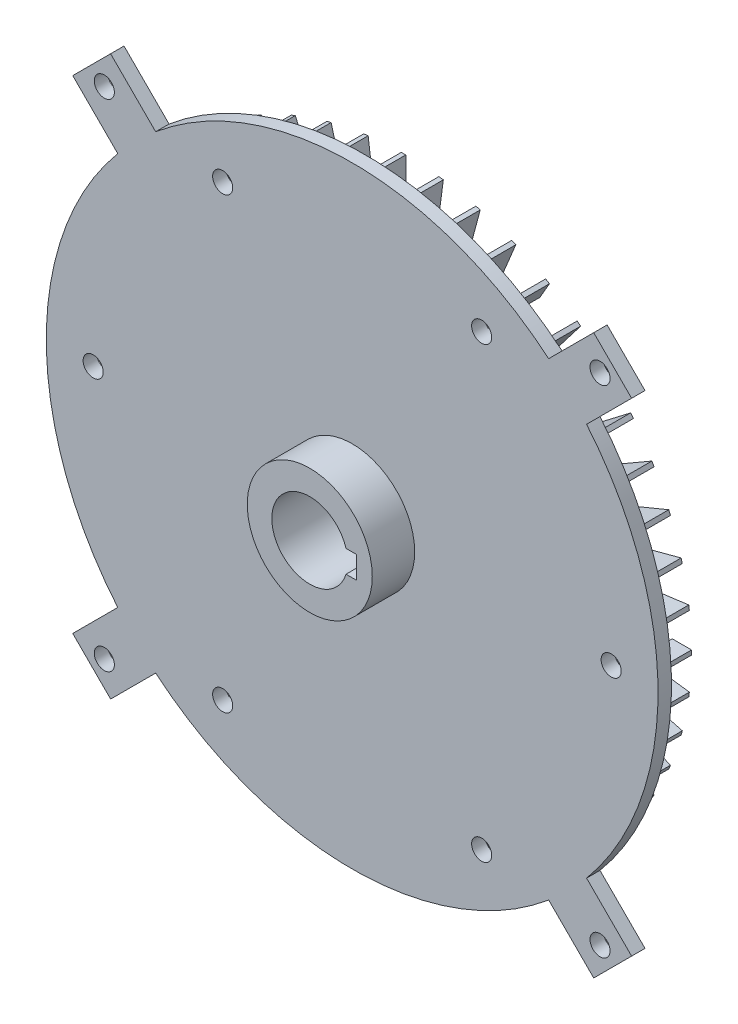
SolidWorks part; units mm, degrees
ref_plane "Спереди" through (0, 0, 0) normal (0, 0, 1) x (1, 0, 0)
ref_plane "Сверху" through (0, 0, 0) normal (0, 1, 0) x (1, 0, 0)
ref_plane "Справа" through (0, 0, 0) normal (1, 0, 0) x (0, 0, -1)
sketch "Эскиз1" plane through (0, 0, 0) normal (0, 0, 1) x (1, 0, 0)
  circle A0 centre (0, 0) radius 68.5
  circle A1 centre (0, 0) radius 8.5
extrude "Heat_spreader" add sketch "Эскиз1" along normal blind 3 from offset 30 offset against normal yes
sketch "Эскиз2" plane through (0, 0, 0) normal (0, 0, 1) x (1, 0, 0)
  line L0 (48.4368, 39.9515) -> (62.579, 54.0937)
  line L1 (62.579, 54.0937) -> (54.0937, 62.579)
  line L2 (54.0937, 62.579) -> (39.9515, 48.4368)
  line L3 (39.9515, 48.4368) -> (48.4368, 39.9515)
  line L4 (-39.9515, 48.4368) -> (-54.0937, 62.579)
  line L5 (-54.0937, 62.579) -> (-62.579, 54.0937)
  line L6 (-62.579, 54.0937) -> (-48.4368, 39.9515)
  line L7 (-48.4368, 39.9515) -> (-39.9515, 48.4368)
  line L8 (-48.4368, -39.9515) -> (-62.579, -54.0937)
  line L9 (-62.579, -54.0937) -> (-54.0937, -62.579)
  line L10 (-54.0937, -62.579) -> (-39.9515, -48.4368)
  line L11 (-39.9515, -48.4368) -> (-48.4368, -39.9515)
  line L12 (39.9515, -48.4368) -> (54.0937, -62.579)
  line L13 (54.0937, -62.579) -> (62.579, -54.0937)
  line L14 (62.579, -54.0937) -> (48.4368, -39.9515)
  line L15 (48.4368, -39.9515) -> (39.9515, -48.4368)
extrude "Tie_rod_ears" add sketch "Эскиз2" along normal blind 3 from offset 30 offset against normal yes
sketch "Эскиз3" plane through (0, 0, 0) normal (0, 0, 1) x (1, 0, 0)
  line L0 (26, -0.5) -> (64.5, -0.5)
  line L1 (64.5, -0.5) -> (64.5, 0.5)
  line L2 (64.5, 0.5) -> (26, 0.5)
  line L3 (26, 0.5) -> (26, -0.5)
  line L4 (25.8428, 2.898) -> (64.0135, 7.9232)
  line L5 (64.0135, 7.9232) -> (63.8829, 8.9147)
  line L6 (63.8829, 8.9147) -> (25.7123, 3.8894)
  line L7 (25.7123, 3.8894) -> (25.8428, 2.898)
  line L8 (25.2435, 6.2463) -> (62.4316, 16.2109)
  line L9 (62.4316, 16.2109) -> (62.1728, 17.1768)
  line L10 (62.1728, 17.1768) -> (24.9847, 7.2123)
  line L11 (24.9847, 7.2123) -> (25.2435, 6.2463)
  line L12 (24.2122, 9.4878) -> (59.7816, 24.2211)
  line L13 (59.7816, 24.2211) -> (59.3989, 25.145)
  line L14 (59.3989, 25.145) -> (23.8295, 10.4117)
  line L15 (23.8295, 10.4117) -> (24.2122, 9.4878)
  line L16 (22.7667, 12.567) -> (56.1086, 31.817)
  line L17 (56.1086, 31.817) -> (55.6086, 32.683)
  line L18 (55.6086, 32.683) -> (22.2667, 13.433)
  line L19 (22.2667, 13.433) -> (22.7667, 12.567)
  line L20 (20.9316, 15.4311) -> (51.4757, 38.8684)
  line L21 (51.4757, 38.8684) -> (50.8669, 39.6618)
  line L22 (50.8669, 39.6618) -> (20.3228, 16.2245)
  line L23 (20.3228, 16.2245) -> (20.9316, 15.4311)
  line L24 (18.7383, 18.0312) -> (45.9619, 45.2548)
  line L25 (45.9619, 45.2548) -> (45.2548, 45.9619)
  line L26 (45.2548, 45.9619) -> (18.0312, 18.7383)
  line L27 (18.0312, 18.7383) -> (18.7383, 18.0312)
  line L28 (16.2245, 20.3228) -> (39.6618, 50.8669)
  line L29 (39.6618, 50.8669) -> (38.8684, 51.4757)
  line L30 (38.8684, 51.4757) -> (15.4311, 20.9316)
  line L31 (15.4311, 20.9316) -> (16.2245, 20.3228)
  line L32 (13.433, 22.2667) -> (32.683, 55.6086)
  line L33 (32.683, 55.6086) -> (31.817, 56.1086)
  line L34 (31.817, 56.1086) -> (12.567, 22.7667)
  line L35 (12.567, 22.7667) -> (13.433, 22.2667)
  line L36 (10.4117, 23.8295) -> (25.145, 59.3989)
  line L37 (25.145, 59.3989) -> (24.2211, 59.7816)
  line L38 (24.2211, 59.7816) -> (9.4878, 24.2122)
  line L39 (9.4878, 24.2122) -> (10.4117, 23.8295)
  line L40 (7.2123, 24.9847) -> (17.1768, 62.1728)
  line L41 (17.1768, 62.1728) -> (16.2109, 62.4316)
  line L42 (16.2109, 62.4316) -> (6.2463, 25.2435)
  line L43 (6.2463, 25.2435) -> (7.2123, 24.9847)
  line L44 (3.8894, 25.7123) -> (8.9147, 63.8829)
  line L45 (8.9147, 63.8829) -> (7.9232, 64.0135)
  line L46 (7.9232, 64.0135) -> (2.898, 25.8428)
  line L47 (2.898, 25.8428) -> (3.8894, 25.7123)
  line L48 (0.5, 26) -> (0.5, 64.5)
  line L49 (0.5, 64.5) -> (-0.5, 64.5)
  line L50 (-0.5, 64.5) -> (-0.5, 26)
  line L51 (-0.5, 26) -> (0.5, 26)
  line L52 (-2.898, 25.8428) -> (-7.9232, 64.0135)
  line L53 (-7.9232, 64.0135) -> (-8.9147, 63.8829)
  line L54 (-8.9147, 63.8829) -> (-3.8894, 25.7123)
  line L55 (-3.8894, 25.7123) -> (-2.898, 25.8428)
  line L56 (-6.2463, 25.2435) -> (-16.2109, 62.4316)
  line L57 (-16.2109, 62.4316) -> (-17.1768, 62.1728)
  line L58 (-17.1768, 62.1728) -> (-7.2123, 24.9847)
  line L59 (-7.2123, 24.9847) -> (-6.2463, 25.2435)
  line L60 (-9.4878, 24.2122) -> (-24.2211, 59.7816)
  line L61 (-24.2211, 59.7816) -> (-25.145, 59.3989)
  line L62 (-25.145, 59.3989) -> (-10.4117, 23.8295)
  line L63 (-10.4117, 23.8295) -> (-9.4878, 24.2122)
  line L64 (-12.567, 22.7667) -> (-31.817, 56.1086)
  line L65 (-31.817, 56.1086) -> (-32.683, 55.6086)
  line L66 (-32.683, 55.6086) -> (-13.433, 22.2667)
  line L67 (-13.433, 22.2667) -> (-12.567, 22.7667)
  line L68 (-15.4311, 20.9316) -> (-38.8684, 51.4757)
  line L69 (-38.8684, 51.4757) -> (-39.6618, 50.8669)
  line L70 (-39.6618, 50.8669) -> (-16.2245, 20.3228)
  line L71 (-16.2245, 20.3228) -> (-15.4311, 20.9316)
  line L72 (-18.0312, 18.7383) -> (-45.2548, 45.9619)
  line L73 (-45.2548, 45.9619) -> (-45.9619, 45.2548)
  line L74 (-45.9619, 45.2548) -> (-18.7383, 18.0312)
  line L75 (-18.7383, 18.0312) -> (-18.0312, 18.7383)
  line L76 (-20.3228, 16.2245) -> (-50.8669, 39.6618)
  line L77 (-50.8669, 39.6618) -> (-51.4757, 38.8684)
  line L78 (-51.4757, 38.8684) -> (-20.9316, 15.4311)
  line L79 (-20.9316, 15.4311) -> (-20.3228, 16.2245)
  line L80 (-22.2667, 13.433) -> (-55.6086, 32.683)
  line L81 (-55.6086, 32.683) -> (-56.1086, 31.817)
  line L82 (-56.1086, 31.817) -> (-22.7667, 12.567)
  line L83 (-22.7667, 12.567) -> (-22.2667, 13.433)
  line L84 (-23.8295, 10.4117) -> (-59.3989, 25.145)
  line L85 (-59.3989, 25.145) -> (-59.7816, 24.2211)
  line L86 (-59.7816, 24.2211) -> (-24.2122, 9.4878)
  line L87 (-24.2122, 9.4878) -> (-23.8295, 10.4117)
  line L88 (-24.9847, 7.2123) -> (-62.1728, 17.1768)
  line L89 (-62.1728, 17.1768) -> (-62.4316, 16.2109)
  line L90 (-62.4316, 16.2109) -> (-25.2435, 6.2463)
  line L91 (-25.2435, 6.2463) -> (-24.9847, 7.2123)
  line L92 (-25.7123, 3.8894) -> (-63.8829, 8.9147)
  line L93 (-63.8829, 8.9147) -> (-64.0135, 7.9232)
  line L94 (-64.0135, 7.9232) -> (-25.8428, 2.898)
  line L95 (-25.8428, 2.898) -> (-25.7123, 3.8894)
  line L96 (-26, 0.5) -> (-64.5, 0.5)
  line L97 (-64.5, 0.5) -> (-64.5, -0.5)
  line L98 (-64.5, -0.5) -> (-26, -0.5)
  line L99 (-26, -0.5) -> (-26, 0.5)
  line L100 (-25.8428, -2.898) -> (-64.0135, -7.9232)
  line L101 (-64.0135, -7.9232) -> (-63.8829, -8.9147)
  line L102 (-63.8829, -8.9147) -> (-25.7123, -3.8894)
  line L103 (-25.7123, -3.8894) -> (-25.8428, -2.898)
  line L104 (-25.2435, -6.2463) -> (-62.4316, -16.2109)
  line L105 (-62.4316, -16.2109) -> (-62.1728, -17.1768)
  line L106 (-62.1728, -17.1768) -> (-24.9847, -7.2123)
  line L107 (-24.9847, -7.2123) -> (-25.2435, -6.2463)
  line L108 (-24.2122, -9.4878) -> (-59.7816, -24.2211)
  line L109 (-59.7816, -24.2211) -> (-59.3989, -25.145)
  line L110 (-59.3989, -25.145) -> (-23.8295, -10.4117)
  line L111 (-23.8295, -10.4117) -> (-24.2122, -9.4878)
  line L112 (-22.7667, -12.567) -> (-56.1086, -31.817)
  line L113 (-56.1086, -31.817) -> (-55.6086, -32.683)
  line L114 (-55.6086, -32.683) -> (-22.2667, -13.433)
  line L115 (-22.2667, -13.433) -> (-22.7667, -12.567)
  line L116 (-20.9316, -15.4311) -> (-51.4757, -38.8684)
  line L117 (-51.4757, -38.8684) -> (-50.8669, -39.6618)
  line L118 (-50.8669, -39.6618) -> (-20.3228, -16.2245)
  line L119 (-20.3228, -16.2245) -> (-20.9316, -15.4311)
  line L120 (-18.7383, -18.0312) -> (-45.9619, -45.2548)
  line L121 (-45.9619, -45.2548) -> (-45.2548, -45.9619)
  line L122 (-45.2548, -45.9619) -> (-18.0312, -18.7383)
  line L123 (-18.0312, -18.7383) -> (-18.7383, -18.0312)
  line L124 (-16.2245, -20.3228) -> (-39.6618, -50.8669)
  line L125 (-39.6618, -50.8669) -> (-38.8684, -51.4757)
  line L126 (-38.8684, -51.4757) -> (-15.4311, -20.9316)
  line L127 (-15.4311, -20.9316) -> (-16.2245, -20.3228)
  line L128 (-13.433, -22.2667) -> (-32.683, -55.6086)
  line L129 (-32.683, -55.6086) -> (-31.817, -56.1086)
  line L130 (-31.817, -56.1086) -> (-12.567, -22.7667)
  line L131 (-12.567, -22.7667) -> (-13.433, -22.2667)
  line L132 (-10.4117, -23.8295) -> (-25.145, -59.3989)
  line L133 (-25.145, -59.3989) -> (-24.2211, -59.7816)
  line L134 (-24.2211, -59.7816) -> (-9.4878, -24.2122)
  line L135 (-9.4878, -24.2122) -> (-10.4117, -23.8295)
  line L136 (-7.2123, -24.9847) -> (-17.1768, -62.1728)
  line L137 (-17.1768, -62.1728) -> (-16.2109, -62.4316)
  line L138 (-16.2109, -62.4316) -> (-6.2463, -25.2435)
  line L139 (-6.2463, -25.2435) -> (-7.2123, -24.9847)
  line L140 (-3.8894, -25.7123) -> (-8.9147, -63.8829)
  line L141 (-8.9147, -63.8829) -> (-7.9232, -64.0135)
  line L142 (-7.9232, -64.0135) -> (-2.898, -25.8428)
  line L143 (-2.898, -25.8428) -> (-3.8894, -25.7123)
  line L144 (-0.5, -26) -> (-0.5, -64.5)
  line L145 (-0.5, -64.5) -> (0.5, -64.5)
  line L146 (0.5, -64.5) -> (0.5, -26)
  line L147 (0.5, -26) -> (-0.5, -26)
  line L148 (2.898, -25.8428) -> (7.9232, -64.0135)
  line L149 (7.9232, -64.0135) -> (8.9147, -63.8829)
  line L150 (8.9147, -63.8829) -> (3.8894, -25.7123)
  line L151 (3.8894, -25.7123) -> (2.898, -25.8428)
  line L152 (6.2463, -25.2435) -> (16.2109, -62.4316)
  line L153 (16.2109, -62.4316) -> (17.1768, -62.1728)
  line L154 (17.1768, -62.1728) -> (7.2123, -24.9847)
  line L155 (7.2123, -24.9847) -> (6.2463, -25.2435)
  line L156 (9.4878, -24.2122) -> (24.2211, -59.7816)
  line L157 (24.2211, -59.7816) -> (25.145, -59.3989)
  line L158 (25.145, -59.3989) -> (10.4117, -23.8295)
  line L159 (10.4117, -23.8295) -> (9.4878, -24.2122)
  line L160 (12.567, -22.7667) -> (31.817, -56.1086)
  line L161 (31.817, -56.1086) -> (32.683, -55.6086)
  line L162 (32.683, -55.6086) -> (13.433, -22.2667)
  line L163 (13.433, -22.2667) -> (12.567, -22.7667)
  line L164 (15.4311, -20.9316) -> (38.8684, -51.4757)
  line L165 (38.8684, -51.4757) -> (39.6618, -50.8669)
  line L166 (39.6618, -50.8669) -> (16.2245, -20.3228)
  line L167 (16.2245, -20.3228) -> (15.4311, -20.9316)
  line L168 (18.0312, -18.7383) -> (45.2548, -45.9619)
  line L169 (45.2548, -45.9619) -> (45.9619, -45.2548)
  line L170 (45.9619, -45.2548) -> (18.7383, -18.0312)
  line L171 (18.7383, -18.0312) -> (18.0312, -18.7383)
  line L172 (20.3228, -16.2245) -> (50.8669, -39.6618)
  line L173 (50.8669, -39.6618) -> (51.4757, -38.8684)
  line L174 (51.4757, -38.8684) -> (20.9316, -15.4311)
  line L175 (20.9316, -15.4311) -> (20.3228, -16.2245)
  line L176 (22.2667, -13.433) -> (55.6086, -32.683)
  line L177 (55.6086, -32.683) -> (56.1086, -31.817)
  line L178 (56.1086, -31.817) -> (22.7667, -12.567)
  line L179 (22.7667, -12.567) -> (22.2667, -13.433)
  line L180 (23.8295, -10.4117) -> (59.3989, -25.145)
  line L181 (59.3989, -25.145) -> (59.7816, -24.2211)
  line L182 (59.7816, -24.2211) -> (24.2122, -9.4878)
  line L183 (24.2122, -9.4878) -> (23.8295, -10.4117)
  line L184 (24.9847, -7.2123) -> (62.1728, -17.1768)
  line L185 (62.1728, -17.1768) -> (62.4316, -16.2109)
  line L186 (62.4316, -16.2109) -> (25.2435, -6.2463)
  line L187 (25.2435, -6.2463) -> (24.9847, -7.2123)
  line L188 (25.7123, -3.8894) -> (63.8829, -8.9147)
  line L189 (63.8829, -8.9147) -> (64.0135, -7.9232)
  line L190 (64.0135, -7.9232) -> (25.8428, -2.898)
  line L191 (25.8428, -2.898) -> (25.7123, -3.8894)
extrude "Cooling_fins" add sketch "Эскиз3" along normal blind 8.5 from offset 38.5 offset against normal yes
sketch "Эскиз4" plane through (0, 0, 0) normal (0, 0, 1) x (1, 0, 0)
  circle A0 centre (55.5079, 55.5079) radius 2.25
  circle A1 centre (-55.5079, 55.5079) radius 2.25
  circle A2 centre (-55.5079, -55.5079) radius 2.25
  circle A3 centre (55.5079, -55.5079) radius 2.25
  circle A4 centre (58, 0) radius 2.25
  circle A5 centre (29, 50.2295) radius 2.25
  circle A6 centre (-29, 50.2295) radius 2.25
  circle A7 centre (-58, 0) radius 2.25
  circle A8 centre (-29, -50.2295) radius 2.25
  circle A9 centre (29, -50.2295) radius 2.25
extrude "Through_holes" cut sketch "Эскиз4" against normal mid plane 200
sketch "Эскиз5" plane through (0, 0, 0) normal (0, 0, 1) x (1, 0, 0)
  circle A0 centre (0, 0) radius 14
  circle A1 centre (0, 0) radius 8.5
extrude "Keyed_reaction_collar" add sketch "Эскиз5" along normal blind 12.5 from offset 30 offset against normal yes
sketch "Эскиз6" plane through (0, 0, 0) normal (0, 0, 1) x (1, 0, 0)
  line L0 (5.5, -2.5) -> (10.5, -2.5)
  line L1 (10.5, -2.5) -> (10.5, 2.5)
  line L2 (10.5, 2.5) -> (5.5, 2.5)
  line L3 (5.5, 2.5) -> (5.5, -2.5)
extrude "Collar_keyway" cut sketch "Эскиз6" along normal blind 12.5 from offset 30 offset against normal yes
